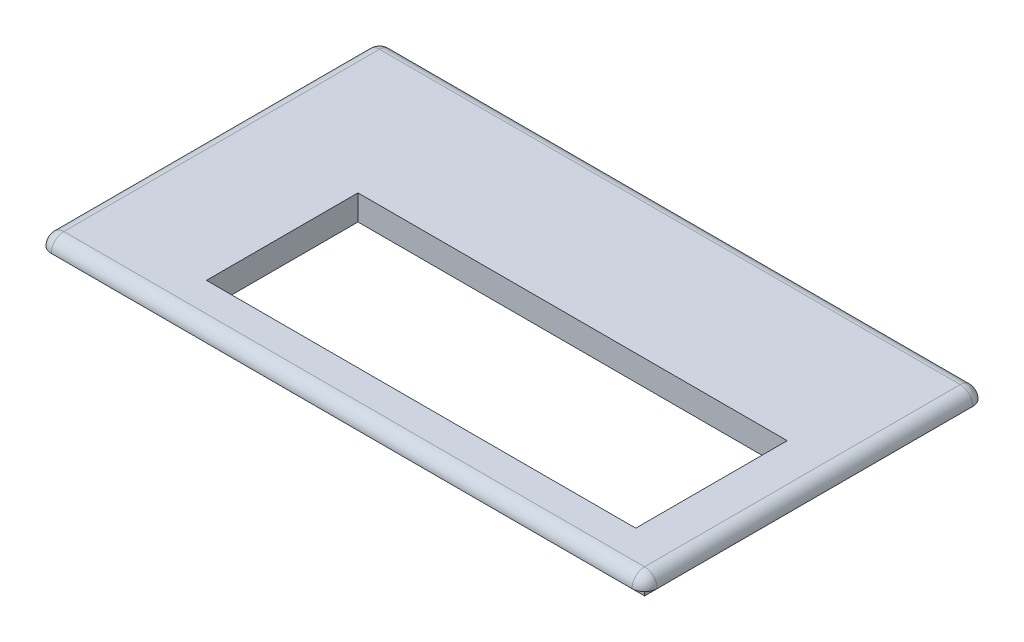
SolidWorks part; units mm, degrees
ref_plane "正面" through (0, 0, 0) normal (0, 0, 1) x (1, 0, 0)
ref_plane "平面" through (0, 0, 0) normal (0, 1, 0) x (1, 0, 0)
ref_plane "右側面" through (0, 0, 0) normal (1, 0, 0) x (0, 0, -1)
sketch "ｽｹｯﾁ1" plane through (0, 0, 0) normal (0, 1, 0) x (1, 0, 0)
  line L0 (-25.8657, 13.1153) -> (20.1343, 13.1153)
  line L1 (-25.8657, 13.1153) -> (-25.8657, -11.8847)
  line L2 (20.1343, 13.1153) -> (20.1343, -11.8847)
  line L3 (-25.8657, -11.8847) -> (20.1343, -11.8847)
  dimension "D1" = 46
  dimension "D2" = 25
extrude "ﾎﾞｽ - 押し出し1" add sketch "ｽｹｯﾁ1" along normal blind 1
sketch "ｽｹｯﾁ2" plane through (0, 1, 0) normal (0, 1, 0) x (1, 0, 0)
  line L0 (-26.8657, 14.1153) -> (21.1343, 14.1153)
  line L1 (-26.8657, 14.1153) -> (-26.8657, -12.8847)
  line L2 (21.1343, 14.1153) -> (21.1343, -12.8847)
  line L3 (-26.8657, -12.8847) -> (21.1343, -12.8847)
  line L6 (20.1343, -11.8847) -> (20.1343, 13.1153) construction
  line L7 (20.1343, 13.1153) -> (-25.8657, 13.1153) construction
  point P4 (-2.8657, 0.6153)
  point P8 (-2.8657, 0.6153)
  dimension "D1" = 48
  dimension "D2" = 27
  dimension "D3" = 24
  dimension "D4" = 13.5
  dimension "D5" = 23
  dimension "D6" = 12.5
extrude "ﾎﾞｽ - 押し出し2" add sketch "ｽｹｯﾁ2" along normal blind 1
fillet "ﾌｨﾚｯﾄ1" radius 1 4 edges at (-26.8657, 2, -0.6153) (-2.8657, 2, 12.8847) (-2.8657, 2, -14.1153) (21.1343, 2, -0.6153)
sketch "ｽｹｯﾁ3" plane through (0, 2, 0) normal (0, 1, 0) x (1, 0, 0)
  line L0 (-16.8657, 2.4153) -> (17.1343, 2.4153)
  line L1 (-16.8657, 2.4153) -> (-16.8657, -9.5847)
  line L2 (17.1343, 2.4153) -> (17.1343, -9.5847)
  line L3 (-16.8657, -9.5847) -> (17.1343, -9.5847)
  line L5 (-25.8657, -11.8847) -> (20.1343, -11.8847) construction
  line L6 (20.1343, -11.8847) -> (20.1343, 13.1153) construction
  dimension "D1" = 34
  dimension "D2" = 12
  dimension "D3" = 3
  dimension "D4" = 2.3
extrude "ｶｯﾄ - 押し出し2" cut sketch "ｽｹｯﾁ3" against normal blind 2 contours L0 L2 L3 L1
